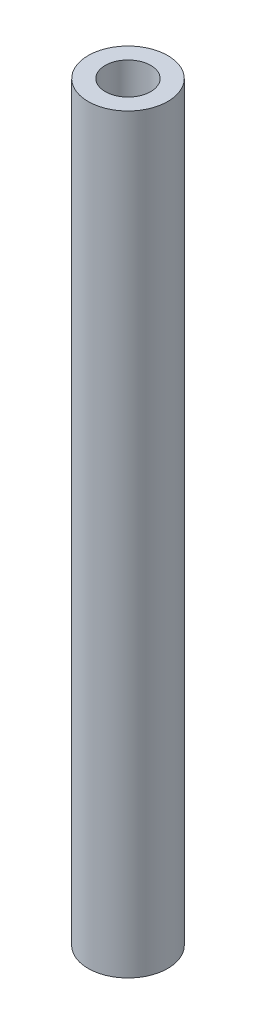
SolidWorks part; units mm, degrees
ref_plane "Plano frontal" through (0, 0, 0) normal (0, 0, 1) x (1, 0, 0)
ref_plane "Plano superior" through (0, 0, 0) normal (0, 1, 0) x (1, 0, 0)
ref_plane "Plano direito" through (0, 0, 0) normal (1, 0, 0) x (0, 0, -1)
ref_plane "Plano1" through (0, 0, 0) normal (0, 0, -1) x (-1, 0, 0)
sketch "Esboço1" plane through (0, 0, 0) normal (0, 0, -1) x (-1, 0, 0)
  line L0 (53.2146, -66) -> (54.7146, -66)
  line L1 (54.7146, -66) -> (54.7146, 0)
  line L2 (54.7146, 0) -> (53.2146, 0)
  line L3 (53.2146, 0) -> (53.2146, -66)
  line L4 (56.7146, -66) -> (56.7146, 0) construction
  point P6 (0, 0)
  dimension "D1" = 2
  dimension "D2" = 3.5
  dimension "D3" = 66
revolve "Revolução1" add sketch "Esboço1" angle 360 about L4 reverse direction yes
